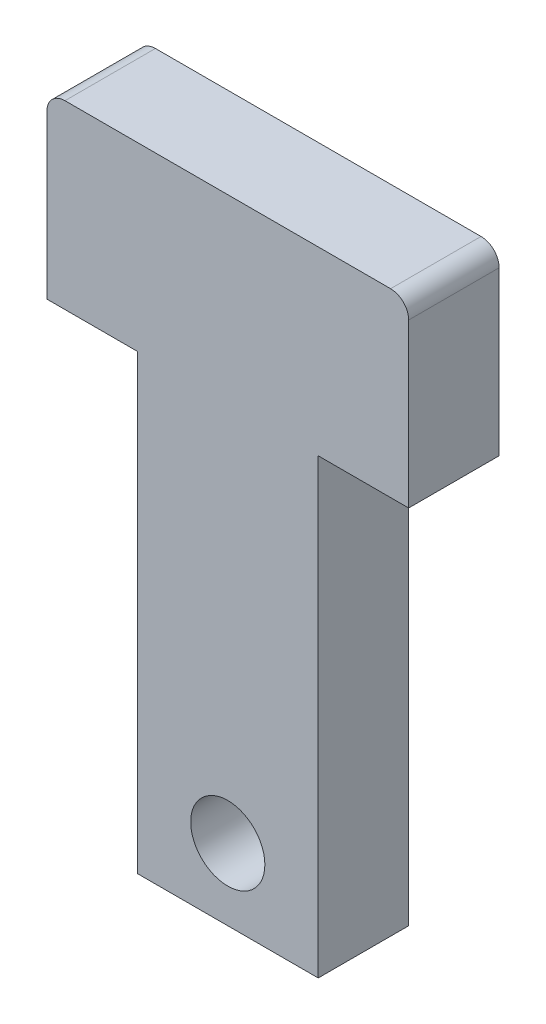
SolidWorks part; units mm, degrees
ref_plane "前基準面" through (0, 0, 0) normal (0, 0, 1) x (1, 0, 0)
ref_plane "上基準面" through (0, 0, 0) normal (0, 1, 0) x (1, 0, 0)
ref_plane "右基準面" through (0, 0, 0) normal (1, 0, 0) x (0, 0, -1)
sketch "草圖1" plane through (0, 0, 0) normal (0, 0, 1) x (1, 0, 0)
  line L0 (-5, -4.5) -> (-10, -4.5)
  line L1 (9, 5.5) -> (-9, 5.5)
  line L2 (10, 4.5) -> (10, -4.5)
  line L3 (10, -4.5) -> (5, -4.5)
  line L4 (-10, 4.5) -> (-10, -4.5)
  line L5 (0, -4.801) -> (0, 5.5) construction
  line L6 (10, 0) -> (-10, 0) construction
  line L7 (5, -29.5) -> (-5, -29.5)
  line L8 (5, -29.5) -> (5, -4.5)
  line L10 (-5, -29.5) -> (-5, -4.5)
  line L11 (0, -4.801) -> (0, -29.5) construction
  line L12 (5, -17) -> (-5, -17) construction
  circle A0 centre (0, -25.55) radius 2.05
  arc A1 (9, 5.5) -> (10, 4.5) centre (9, 4.5) cw
  arc A2 (-9, 5.5) -> (-10, 4.5) centre (-9, 4.5) ccw
  point P0 (0, 0)
  point P4 (0, -17)
  point P14 (0, -23.5)
  point P19 (10, 5.5)
  point P22 (-10, 5.5)
  dimension "D5" = 4.1
  dimension "D7" = 1
  dimension "D1" = 10
  dimension "D2" = 20
  dimension "D3" = 10
  dimension "D4" = 25
  dimension "D6" = 19
extrude "填料-伸長1" add sketch "草圖1" along normal blind 5
